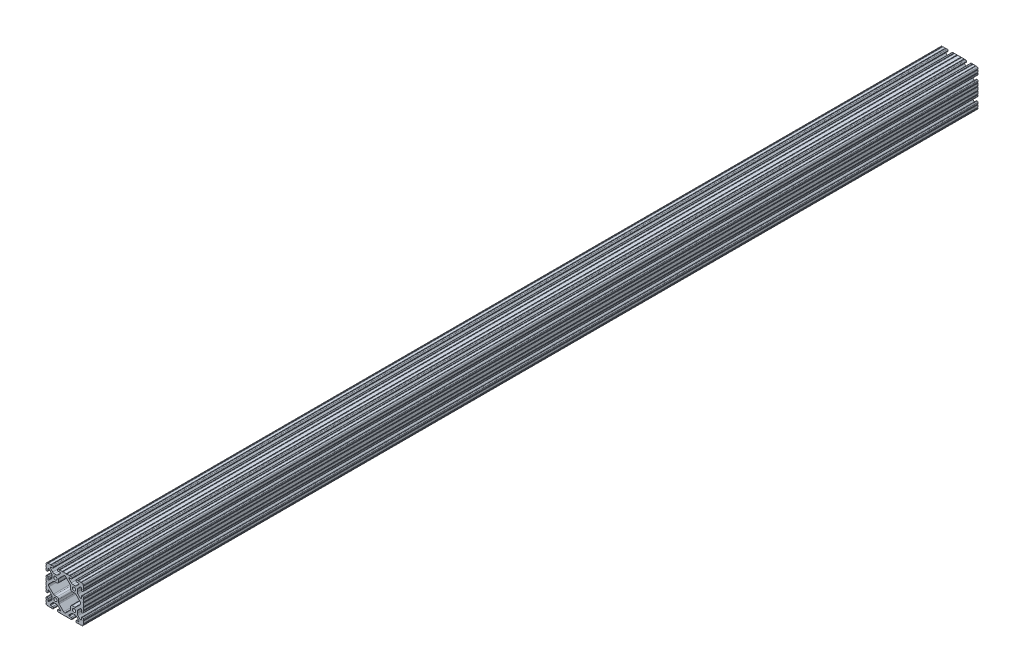
SolidWorks part; units mm, degrees
ref_plane "Front Plane" through (0, 0, 0) normal (0, 0, 1) x (1, 0, 0)
ref_plane "Top Plane" through (0, 0, 0) normal (0, 1, 0) x (1, 0, 0)
ref_plane "Right Plane" through (0, 0, 0) normal (1, 0, 0) x (0, 0, -1)
sketch "Sketch1" plane through (0, 0, 0) normal (0, 0, 1) x (1, 0, 0)
  line L0 (0, 38.1) -> (0, -38.1) construction
  line L1 (-38.1, -38.1) -> (38.1, -38.1) construction
  line L2 (-38.1, -38.1) -> (-38.1, 38.1) construction
  line L3 (-38.1, 38.1) -> (38.1, 38.1) construction
  line L4 (38.1, -38.1) -> (38.1, 38.1) construction
  line L5 (0, 38.1) -> (0, -38.1) construction
  line L6 (-38.1, 0) -> (38.1, 0) construction
  line L7 (-19.05, 19.05) -> (19.05, 19.05) construction
  line L8 (-19.05, 19.05) -> (-19.05, -19.05) construction
  line L9 (-19.05, -19.05) -> (19.05, -19.05) construction
  line L10 (19.05, 19.05) -> (19.05, -19.05) construction
  line L11 (-23.114, 38.1) -> (-23.114, -38.1) construction
  line L12 (-23.114, -38.1) -> (-14.986, 38.1) construction
  line L13 (-14.986, 38.1) -> (-14.986, -38.1) construction
  circle A0 centre (19.05, 19.05) radius 3.3274
  point P0 (0, 0)
  point P9 (0, 0)
  point P12 (-19.05, 0)
  line B0 (-11.3637, -22.8433) -> (-2.0515, -32.1555)
  line B1 (-12.2936, -15.4686) -> (-12.2936, -20.5983)
  line B2 (-20.769, -12.2936) -> (-15.4686, -12.2936)
  line B3 (-31.9021, -2.4756) -> (-23.0141, -11.3637)
  line B4 (-23.0141, 11.3637) -> (-31.9021, 2.4756)
  line B5 (-15.4686, 12.2936) -> (-20.769, 12.2936)
  line B6 (-12.2936, 20.5983) -> (-12.2936, 15.4686)
  line B7 (-2.0515, 32.1555) -> (-11.3637, 22.8433)
  line B8 (11.3637, 22.8433) -> (2.0515, 32.1555)
  line B9 (12.2936, 15.4686) -> (12.2936, 20.5983)
  line B10 (20.769, 12.2936) -> (15.4686, 12.2936)
  line B11 (31.9021, 2.4756) -> (23.0141, 11.3637)
  line B12 (23.0141, -11.3637) -> (31.9021, -2.4756)
  line B13 (15.4686, -12.2936) -> (20.769, -12.2936)
  line B14 (12.2936, -20.5983) -> (12.2936, -15.4686)
  line B15 (2.0515, -32.1555) -> (11.3637, -22.8433)
  line B16 (-4.7773, 38.1) -> (-9.6053, 38.1)
  line B17 (-11.1289, 38.1) -> (-13.4112, 38.1)
  line B18 (-14.986, 36.5252) -> (-14.986, 35.6108)
  line B19 (-13.4112, 34.036) -> (-9.652, 34.036)
  line B20 (-8.763, 33.147) -> (-8.763, 32.4935)
  line B21 (-9.0234, 31.8649) -> (-13.6907, 27.1976)
  line B22 (-17.0493, 25.8064) -> (-21.0507, 25.8064)
  line B23 (-24.4093, 27.1976) -> (-29.1002, 31.8885)
  line B24 (-29.337, 32.7207) -> (-29.337, 33.147)
  line B25 (-28.448, 34.036) -> (-24.6888, 34.036)
  line B26 (-23.114, 35.6108) -> (-23.114, 36.5252)
  line B27 (-24.6888, 38.1) -> (-27.0772, 38.1)
  line B28 (-28.6011, 38.1) -> (-33.4288, 38.1)
  line B29 (-38.1, 33.373) -> (-38.1, 28.5453)
  line B30 (-38.1, 27.0238) -> (-38.1, 24.6302)
  line B31 (-36.5252, 23.0554) -> (-35.6108, 23.0554)
  line B32 (-34.036, 24.6302) -> (-34.036, 28.448)
  line B33 (-33.147, 29.337) -> (-32.6643, 29.337)
  line B34 (-32.0357, 29.0766) -> (-27.1976, 24.2385)
  line B35 (-25.8064, 20.8799) -> (-25.8064, 17.2201)
  line B36 (-27.1976, 13.8615) -> (-31.9489, 9.1101)
  line B37 (-32.7869, 8.763) -> (-33.0603, 8.763)
  line B38 (-34.036, 9.7387) -> (-34.036, 13.4698)
  line B39 (-35.6108, 15.0446) -> (-36.5252, 15.0446)
  line B40 (-38.1, 13.4698) -> (-38.1, 11.075)
  line B41 (-38.1, 9.552) -> (-38.1, 4.7238)
  line B42 (-38.1, 3.2007) -> (-38.1, -3.2007)
  line B43 (-38.1, -4.7238) -> (-38.1, -9.552)
  line B44 (-38.1, -11.075) -> (-38.1, -13.4698)
  line B45 (-36.5252, -15.0446) -> (-35.6108, -15.0446)
  line B46 (-34.036, -13.4698) -> (-34.036, -9.7387)
  line B47 (-33.0603, -8.763) -> (-32.7869, -8.763)
  line B48 (-31.9489, -9.1101) -> (-27.1976, -13.8615)
  line B49 (-25.8064, -17.2201) -> (-25.8064, -20.8799)
  line B50 (-27.1976, -24.2385) -> (-32.0357, -29.0766)
  line B51 (-32.6643, -29.337) -> (-33.147, -29.337)
  line B52 (-34.036, -28.448) -> (-34.036, -24.6302)
  line B53 (-35.6108, -23.0554) -> (-36.5252, -23.0554)
  line B54 (-38.1, -24.6302) -> (-38.1, -27.0238)
  line B55 (-38.1, -28.5453) -> (-38.1, -33.373)
  line B56 (-33.4288, -38.1) -> (-28.6011, -38.1)
  line B57 (-27.0772, -38.1) -> (-24.6888, -38.1)
  line B58 (-23.114, -36.5252) -> (-23.114, -35.6108)
  line B59 (-24.6888, -34.036) -> (-28.448, -34.036)
  line B60 (-29.337, -33.147) -> (-29.337, -32.7207)
  line B61 (-29.1002, -31.8885) -> (-24.4093, -27.1976)
  line B62 (-21.0507, -25.8064) -> (-17.0493, -25.8064)
  line B63 (-13.6907, -27.1976) -> (-9.0234, -31.8649)
  line B64 (-8.763, -32.4935) -> (-8.763, -33.147)
  line B65 (-9.652, -34.036) -> (-13.4112, -34.036)
  line B66 (-14.986, -35.6108) -> (-14.986, -36.5252)
  line B67 (-13.4112, -38.1) -> (-11.1289, -38.1)
  line B68 (-9.6053, -38.1) -> (-4.7773, -38.1)
  line B69 (-3.2537, -38.1) -> (3.2537, -38.1)
  line B70 (4.7773, -38.1) -> (9.6053, -38.1)
  line B71 (11.1289, -38.1) -> (13.4112, -38.1)
  line B72 (14.986, -36.5252) -> (14.986, -35.6108)
  line B73 (13.4112, -34.036) -> (9.652, -34.036)
  line B74 (8.763, -33.147) -> (8.763, -32.4935)
  line B75 (9.0234, -31.8649) -> (13.6907, -27.1976)
  line B76 (17.0493, -25.8064) -> (21.0507, -25.8064)
  line B77 (24.4093, -27.1976) -> (29.1002, -31.8885)
  line B78 (29.337, -32.7207) -> (29.337, -33.147)
  line B79 (28.448, -34.036) -> (24.6888, -34.036)
  line B80 (23.114, -35.6108) -> (23.114, -36.5252)
  line B81 (24.6888, -38.1) -> (27.0772, -38.1)
  line B82 (28.6011, -38.1) -> (33.4288, -38.1)
  line B83 (38.1, -33.373) -> (38.1, -28.5453)
  line B84 (38.1, -27.0238) -> (38.1, -24.6302)
  line B85 (36.5252, -23.0554) -> (35.6108, -23.0554)
  line B86 (34.036, -24.6302) -> (34.036, -28.448)
  line B87 (33.147, -29.337) -> (32.6643, -29.337)
  line B88 (32.0357, -29.0766) -> (27.1976, -24.2385)
  line B89 (25.8064, -20.8799) -> (25.8064, -17.2201)
  line B90 (27.1976, -13.8615) -> (31.9489, -9.1101)
  line B91 (32.7869, -8.763) -> (33.0603, -8.763)
  line B92 (34.036, -9.7387) -> (34.036, -13.4698)
  line B93 (35.6108, -15.0446) -> (36.5252, -15.0446)
  line B94 (38.1, -13.4698) -> (38.1, -11.075)
  line B95 (38.1, -9.552) -> (38.1, -4.7238)
  line B96 (38.1, -3.2007) -> (38.1, 3.2007)
  line B97 (38.1, 4.7238) -> (38.1, 9.552)
  line B98 (38.1, 11.075) -> (38.1, 13.4698)
  line B99 (36.5252, 15.0446) -> (35.6108, 15.0446)
  line B100 (34.036, 13.4698) -> (34.036, 9.7387)
  line B101 (33.0603, 8.763) -> (32.7869, 8.763)
  line B102 (31.9489, 9.1101) -> (27.1976, 13.8615)
  line B103 (25.8064, 17.2201) -> (25.8064, 20.8799)
  line B104 (27.1976, 24.2385) -> (32.0357, 29.0766)
  line B105 (32.6643, 29.337) -> (33.147, 29.337)
  line B106 (34.036, 28.448) -> (34.036, 24.6302)
  line B107 (35.6108, 23.0554) -> (36.5252, 23.0554)
  line B108 (38.1, 24.6302) -> (38.1, 27.0238)
  line B109 (38.1, 28.5453) -> (38.1, 33.373)
  line B110 (33.4288, 38.1) -> (28.6011, 38.1)
  line B111 (27.0772, 38.1) -> (24.6888, 38.1)
  line B112 (23.114, 36.5252) -> (23.114, 35.6108)
  line B113 (24.6888, 34.036) -> (28.448, 34.036)
  line B114 (29.337, 33.147) -> (29.337, 32.7207)
  line B115 (29.1002, 31.8885) -> (24.4093, 27.1976)
  line B116 (21.0507, 25.8064) -> (17.0493, 25.8064)
  line B117 (13.6907, 27.1976) -> (9.0234, 31.8649)
  line B118 (8.763, 32.4935) -> (8.763, 33.147)
  line B119 (9.652, 34.036) -> (13.4112, 34.036)
  line B120 (14.986, 35.6108) -> (14.986, 36.5252)
  line B121 (13.4112, 38.1) -> (11.1289, 38.1)
  line B122 (9.6053, 38.1) -> (4.7773, 38.1)
  line B123 (3.2537, 38.1) -> (-3.2537, 38.1)
  circle B124 centre (-19.05, 19.05) radius 3.3274
  circle B125 centre (-19.05, -19.05) radius 3.3274
  circle B126 centre (19.05, -19.05) radius 3.3274
  circle B127 centre (19.05, 19.05) radius 3.3274
  arc B128 (0, -33.011) -> (2.0515, -32.1555) centre (-0.0139, -30.09) ccw
  arc B129 (-2.0515, -32.1555) -> (0, -33.011) centre (0.0139, -30.09) ccw
  arc B130 (-12.2936, -20.5983) -> (-11.3637, -22.8433) centre (-9.1186, -20.5983) ccw
  arc B131 (-12.2936, -15.4686) -> (-15.4686, -12.2936) centre (-15.4686, -15.4686) ccw
  arc B132 (-23.0141, -11.3637) -> (-20.769, -12.2936) centre (-20.769, -9.1186) ccw
  arc B133 (-32.7287, 0) -> (-31.9021, -2.4756) centre (-29.8367, -0.4102) ccw
  arc B134 (-31.9021, 2.4756) -> (-32.7287, 0) centre (-29.8367, 0.4102) ccw
  arc B135 (-20.769, 12.2936) -> (-23.0141, 11.3637) centre (-20.769, 9.1186) ccw
  arc B136 (-15.4686, 12.2936) -> (-12.2936, 15.4686) centre (-15.4686, 15.4686) ccw
  arc B137 (-11.3637, 22.8433) -> (-12.2936, 20.5983) centre (-9.1186, 20.5983) ccw
  arc B138 (0, 33.011) -> (-2.0515, 32.1555) centre (0.0139, 30.09) ccw
  arc B139 (2.0515, 32.1555) -> (0, 33.011) centre (-0.0139, 30.09) ccw
  arc B140 (12.2936, 20.5983) -> (11.3637, 22.8433) centre (9.1186, 20.5983) ccw
  arc B141 (12.2936, 15.4686) -> (15.4686, 12.2936) centre (15.4686, 15.4686) ccw
  arc B142 (23.0141, 11.3637) -> (20.769, 12.2936) centre (20.769, 9.1186) ccw
  arc B143 (32.7287, 0) -> (31.9021, 2.4756) centre (29.8367, 0.4102) ccw
  arc B144 (31.9021, -2.4756) -> (32.7287, 0) centre (29.8367, -0.4102) ccw
  arc B145 (20.769, -12.2936) -> (23.0141, -11.3637) centre (20.769, -9.1186) ccw
  arc B146 (15.4686, -12.2936) -> (12.2936, -15.4686) centre (15.4686, -15.4686) ccw
  arc B147 (11.3637, -22.8433) -> (12.2936, -20.5983) centre (9.1186, -20.5983) ccw
  arc B148 (-4.7773, 38.1) -> (-3.2537, 38.1) centre (-4.0155, 38.0824) ccw
  arc B149 (-11.1289, 38.1) -> (-9.6053, 38.1) centre (-10.3671, 38.0824) ccw
  arc B150 (-13.4112, 38.1) -> (-14.986, 36.5252) centre (-13.4112, 36.5252) ccw
  arc B151 (-14.986, 35.6108) -> (-13.4112, 34.036) centre (-13.4112, 35.6108) ccw
  arc B152 (-8.763, 33.147) -> (-9.652, 34.036) centre (-9.652, 33.147) ccw
  arc B153 (-9.0234, 31.8649) -> (-8.763, 32.4935) centre (-9.652, 32.4935) ccw
  arc B154 (-17.0493, 25.8064) -> (-13.6907, 27.1976) centre (-17.0493, 30.5562) ccw
  arc B155 (-24.4093, 27.1976) -> (-21.0507, 25.8064) centre (-21.0507, 30.5562) ccw
  arc B156 (-29.337, 32.7207) -> (-29.1002, 31.8885) centre (-28.4716, 32.5172) ccw
  arc B157 (-28.448, 34.036) -> (-29.337, 33.147) centre (-28.448, 33.147) ccw
  arc B158 (-24.6888, 34.036) -> (-23.114, 35.6108) centre (-24.6888, 35.6108) ccw
  arc B159 (-23.114, 36.5252) -> (-24.6888, 38.1) centre (-24.6888, 36.5252) ccw
  arc B160 (-28.6011, 38.1) -> (-27.0772, 38.1) centre (-27.8392, 38.0824) ccw
  arc B161 (-34.9527, 38.1) -> (-33.4288, 38.1) centre (-34.1907, 38.0824) ccw
  arc B162 (-34.9527, 38.1) -> (-37.0861, 37.1826) centre (-34.8521, 34.9266) ccw
  arc B163 (-37.0861, 37.1826) -> (-38.1, 34.8455) centre (-34.925, 34.8566) ccw
  arc B164 (-38.1, 33.373) -> (-38.1, 34.8455) centre (-37.9035, 34.1092) ccw
  arc B165 (-38.1, 27.0238) -> (-38.1, 28.5453) centre (-37.9035, 27.7845) ccw
  arc B166 (-38.1, 24.6302) -> (-36.5252, 23.0554) centre (-36.5252, 24.6302) ccw
  arc B167 (-35.6108, 23.0554) -> (-34.036, 24.6302) centre (-35.6108, 24.6302) ccw
  arc B168 (-33.147, 29.337) -> (-34.036, 28.448) centre (-33.147, 28.448) ccw
  arc B169 (-32.0357, 29.0766) -> (-32.6643, 29.337) centre (-32.6643, 28.448) ccw
  arc B170 (-25.8064, 20.8799) -> (-27.1976, 24.2385) centre (-30.5562, 20.8799) ccw
  arc B171 (-27.1976, 13.8615) -> (-25.8064, 17.2201) centre (-30.5562, 17.2201) ccw
  arc B172 (-32.7869, 8.763) -> (-31.9489, 9.1101) centre (-32.7869, 9.9481) ccw
  arc B173 (-34.036, 9.7387) -> (-33.0603, 8.763) centre (-33.0603, 9.7387) ccw
  arc B174 (-34.036, 13.4698) -> (-35.6108, 15.0446) centre (-35.6108, 13.4698) ccw
  arc B175 (-36.5252, 15.0446) -> (-38.1, 13.4698) centre (-36.5252, 13.4698) ccw
  arc B176 (-38.1, 9.552) -> (-38.1, 11.075) centre (-37.9035, 10.3135) ccw
  arc B177 (-38.1, 3.2007) -> (-38.1, 4.7238) centre (-37.9035, 3.9622) ccw
  arc B178 (-38.1, -4.7238) -> (-38.1, -3.2007) centre (-37.9035, -3.9622) ccw
  arc B179 (-38.1, -11.075) -> (-38.1, -9.552) centre (-37.9035, -10.3135) ccw
  arc B180 (-38.1, -13.4698) -> (-36.5252, -15.0446) centre (-36.5252, -13.4698) ccw
  arc B181 (-35.6108, -15.0446) -> (-34.036, -13.4698) centre (-35.6108, -13.4698) ccw
  arc B182 (-33.0603, -8.763) -> (-34.036, -9.7387) centre (-33.0603, -9.7387) ccw
  arc B183 (-31.9489, -9.1101) -> (-32.7869, -8.763) centre (-32.7869, -9.9481) ccw
  arc B184 (-25.8064, -17.2201) -> (-27.1976, -13.8615) centre (-30.5562, -17.2201) ccw
  arc B185 (-27.1976, -24.2385) -> (-25.8064, -20.8799) centre (-30.5562, -20.8799) ccw
  arc B186 (-32.6643, -29.337) -> (-32.0357, -29.0766) centre (-32.6643, -28.448) ccw
  arc B187 (-34.036, -28.448) -> (-33.147, -29.337) centre (-33.147, -28.448) ccw
  arc B188 (-34.036, -24.6302) -> (-35.6108, -23.0554) centre (-35.6108, -24.6302) ccw
  arc B189 (-36.5252, -23.0554) -> (-38.1, -24.6302) centre (-36.5252, -24.6302) ccw
  arc B190 (-38.1, -28.5453) -> (-38.1, -27.0238) centre (-37.9035, -27.7845) ccw
  arc B191 (-38.1, -34.8455) -> (-38.1, -33.373) centre (-37.9035, -34.1092) ccw
  arc B192 (-38.1, -34.8455) -> (-37.0861, -37.1826) centre (-34.925, -34.8566) ccw
  arc B193 (-37.0861, -37.1826) -> (-34.9527, -38.1) centre (-34.8521, -34.9266) ccw
  arc B194 (-33.4288, -38.1) -> (-34.9527, -38.1) centre (-34.1907, -38.0824) ccw
  arc B195 (-27.0772, -38.1) -> (-28.6011, -38.1) centre (-27.8392, -38.0824) ccw
  arc B196 (-24.6888, -38.1) -> (-23.114, -36.5252) centre (-24.6888, -36.5252) ccw
  arc B197 (-23.114, -35.6108) -> (-24.6888, -34.036) centre (-24.6888, -35.6108) ccw
  arc B198 (-29.337, -33.147) -> (-28.448, -34.036) centre (-28.448, -33.147) ccw
  arc B199 (-29.1002, -31.8885) -> (-29.337, -32.7207) centre (-28.4716, -32.5172) ccw
  arc B200 (-21.0507, -25.8064) -> (-24.4093, -27.1976) centre (-21.0507, -30.5562) ccw
  arc B201 (-13.6907, -27.1976) -> (-17.0493, -25.8064) centre (-17.0493, -30.5562) ccw
  arc B202 (-8.763, -32.4935) -> (-9.0234, -31.8649) centre (-9.652, -32.4935) ccw
  arc B203 (-9.652, -34.036) -> (-8.763, -33.147) centre (-9.652, -33.147) ccw
  arc B204 (-13.4112, -34.036) -> (-14.986, -35.6108) centre (-13.4112, -35.6108) ccw
  arc B205 (-14.986, -36.5252) -> (-13.4112, -38.1) centre (-13.4112, -36.5252) ccw
  arc B206 (-9.6053, -38.1) -> (-11.1289, -38.1) centre (-10.3671, -38.0824) ccw
  arc B207 (-3.2537, -38.1) -> (-4.7773, -38.1) centre (-4.0155, -38.0824) ccw
  arc B208 (4.7773, -38.1) -> (3.2537, -38.1) centre (4.0155, -38.0824) ccw
  arc B209 (11.1289, -38.1) -> (9.6053, -38.1) centre (10.3671, -38.0824) ccw
  arc B210 (13.4112, -38.1) -> (14.986, -36.5252) centre (13.4112, -36.5252) ccw
  arc B211 (14.986, -35.6108) -> (13.4112, -34.036) centre (13.4112, -35.6108) ccw
  arc B212 (8.763, -33.147) -> (9.652, -34.036) centre (9.652, -33.147) ccw
  arc B213 (9.0234, -31.8649) -> (8.763, -32.4935) centre (9.652, -32.4935) ccw
  arc B214 (17.0493, -25.8064) -> (13.6907, -27.1976) centre (17.0493, -30.5562) ccw
  arc B215 (24.4093, -27.1976) -> (21.0507, -25.8064) centre (21.0507, -30.5562) ccw
  arc B216 (29.337, -32.7207) -> (29.1002, -31.8885) centre (28.4716, -32.5172) ccw
  arc B217 (28.448, -34.036) -> (29.337, -33.147) centre (28.448, -33.147) ccw
  arc B218 (24.6888, -34.036) -> (23.114, -35.6108) centre (24.6888, -35.6108) ccw
  arc B219 (23.114, -36.5252) -> (24.6888, -38.1) centre (24.6888, -36.5252) ccw
  arc B220 (28.6011, -38.1) -> (27.0772, -38.1) centre (27.8392, -38.0824) ccw
  arc B221 (34.9527, -38.1) -> (33.4288, -38.1) centre (34.1907, -38.0824) ccw
  arc B222 (34.9527, -38.1) -> (37.0861, -37.1826) centre (34.8521, -34.9266) ccw
  arc B223 (37.0861, -37.1826) -> (38.1, -34.8455) centre (34.925, -34.8566) ccw
  arc B224 (38.1, -33.373) -> (38.1, -34.8455) centre (37.9035, -34.1092) ccw
  arc B225 (38.1, -27.0238) -> (38.1, -28.5453) centre (37.9035, -27.7845) ccw
  arc B226 (38.1, -24.6302) -> (36.5252, -23.0554) centre (36.5252, -24.6302) ccw
  arc B227 (35.6108, -23.0554) -> (34.036, -24.6302) centre (35.6108, -24.6302) ccw
  arc B228 (33.147, -29.337) -> (34.036, -28.448) centre (33.147, -28.448) ccw
  arc B229 (32.0357, -29.0766) -> (32.6643, -29.337) centre (32.6643, -28.448) ccw
  arc B230 (25.8064, -20.8799) -> (27.1976, -24.2385) centre (30.5562, -20.8799) ccw
  arc B231 (27.1976, -13.8615) -> (25.8064, -17.2201) centre (30.5562, -17.2201) ccw
  arc B232 (32.7869, -8.763) -> (31.9489, -9.1101) centre (32.7869, -9.9481) ccw
  arc B233 (34.036, -9.7387) -> (33.0603, -8.763) centre (33.0603, -9.7387) ccw
  arc B234 (34.036, -13.4698) -> (35.6108, -15.0446) centre (35.6108, -13.4698) ccw
  arc B235 (36.5252, -15.0446) -> (38.1, -13.4698) centre (36.5252, -13.4698) ccw
  arc B236 (38.1, -9.552) -> (38.1, -11.075) centre (37.9035, -10.3135) ccw
  arc B237 (38.1, -3.2007) -> (38.1, -4.7238) centre (37.9035, -3.9622) ccw
  arc B238 (38.1, 4.7238) -> (38.1, 3.2007) centre (37.9035, 3.9622) ccw
  arc B239 (38.1, 11.075) -> (38.1, 9.552) centre (37.9035, 10.3135) ccw
  arc B240 (38.1, 13.4698) -> (36.5252, 15.0446) centre (36.5252, 13.4698) ccw
  arc B241 (35.6108, 15.0446) -> (34.036, 13.4698) centre (35.6108, 13.4698) ccw
  arc B242 (33.0603, 8.763) -> (34.036, 9.7387) centre (33.0603, 9.7387) ccw
  arc B243 (31.9489, 9.1101) -> (32.7869, 8.763) centre (32.7869, 9.9481) ccw
  arc B244 (25.8064, 17.2201) -> (27.1976, 13.8615) centre (30.5562, 17.2201) ccw
  arc B245 (27.1976, 24.2385) -> (25.8064, 20.8799) centre (30.5562, 20.8799) ccw
  arc B246 (32.6643, 29.337) -> (32.0357, 29.0766) centre (32.6643, 28.448) ccw
  arc B247 (34.036, 28.448) -> (33.147, 29.337) centre (33.147, 28.448) ccw
  arc B248 (34.036, 24.6302) -> (35.6108, 23.0554) centre (35.6108, 24.6302) ccw
  arc B249 (36.5252, 23.0554) -> (38.1, 24.6302) centre (36.5252, 24.6302) ccw
  arc B250 (38.1, 28.5453) -> (38.1, 27.0238) centre (37.9035, 27.7845) ccw
  arc B251 (38.1, 34.8455) -> (38.1, 33.373) centre (37.9035, 34.1092) ccw
  arc B252 (38.1, 34.8455) -> (37.0861, 37.1826) centre (34.925, 34.8566) ccw
  arc B253 (37.0861, 37.1826) -> (34.9527, 38.1) centre (34.8521, 34.9266) ccw
  arc B254 (33.4288, 38.1) -> (34.9527, 38.1) centre (34.1907, 38.0824) ccw
  arc B255 (27.0772, 38.1) -> (28.6011, 38.1) centre (27.8392, 38.0824) ccw
  arc B256 (24.6888, 38.1) -> (23.114, 36.5252) centre (24.6888, 36.5252) ccw
  arc B257 (23.114, 35.6108) -> (24.6888, 34.036) centre (24.6888, 35.6108) ccw
  arc B258 (29.337, 33.147) -> (28.448, 34.036) centre (28.448, 33.147) ccw
  arc B259 (29.1002, 31.8885) -> (29.337, 32.7207) centre (28.4716, 32.5172) ccw
  arc B260 (21.0507, 25.8064) -> (24.4093, 27.1976) centre (21.0507, 30.5562) ccw
  arc B261 (13.6907, 27.1976) -> (17.0493, 25.8064) centre (17.0493, 30.5562) ccw
  arc B262 (8.763, 32.4935) -> (9.0234, 31.8649) centre (9.652, 32.4935) ccw
  arc B263 (9.652, 34.036) -> (8.763, 33.147) centre (9.652, 33.147) ccw
  arc B264 (13.4112, 34.036) -> (14.986, 35.6108) centre (13.4112, 35.6108) ccw
  arc B265 (14.986, 36.5252) -> (13.4112, 38.1) centre (13.4112, 36.5252) ccw
  arc B266 (9.6053, 38.1) -> (11.1289, 38.1) centre (10.3671, 38.0824) ccw
  arc B267 (3.2537, 38.1) -> (4.7773, 38.1) centre (4.0155, 38.0824) ccw
  dimension "Center Hole Diameter" = 6.6548
  dimension "Rail Width" = 76.2
  dimension "Rail Height" = 76.2
  dimension "T-Slot Width" = 8.128
sketch_block_instance "Block1-1"
sketch_block "Block1"
sketch "Sketch2" plane through (0, 0, 0) normal (1, 0, 0) x (0, 0, -1)
  line L0 (-914.4, 0) -> (914.4, 0) construction
  line L1 (-914.4, 38.1) -> (-914.4, -38.1) construction
  line L2 (-914.4, -38.1) -> (914.4, -38.1) construction
  line L3 (914.4, -38.1) -> (914.4, 38.1) construction
  line L4 (-812.8, 0) -> (-812.8, 38.1) construction
  line L5 (-812.8, 38.1) -> (812.8, 38.1) construction
  line L6 (812.8, 38.1) -> (812.8, 0) construction
  point P5 (812.8, 0)
  point P10 (-812.8, 0)
  dimension "D1" = 101.6
  dimension "Length" = 1828.8
  dimension "D2" = 101.6
sketch "Sketch3" plane through (0, 0, 0) normal (0, 0, 1) x (1, 0, 0)
  line L0 (-11.3637, -22.8433) -> (-2.0515, -32.1555) construction
  line L1 (-12.2936, -15.4686) -> (-12.2936, -20.5983) construction
  line L2 (-20.769, -12.2936) -> (-15.4686, -12.2936) construction
  line L3 (-31.9021, -2.4756) -> (-23.0141, -11.3637) construction
  line L4 (-23.0141, 11.3637) -> (-31.9021, 2.4756) construction
  line L5 (-15.4686, 12.2936) -> (-20.769, 12.2936) construction
  line L6 (-12.2936, 20.5983) -> (-12.2936, 15.4686) construction
  line L7 (-2.0515, 32.1555) -> (-11.3637, 22.8433) construction
  line L8 (11.3637, 22.8433) -> (2.0515, 32.1555) construction
  line L9 (12.2936, 15.4686) -> (12.2936, 20.5983) construction
  line L10 (20.769, 12.2936) -> (15.4686, 12.2936) construction
  line L11 (31.9021, 2.4756) -> (23.0141, 11.3637) construction
  line L12 (23.0141, -11.3637) -> (31.9021, -2.4756) construction
  line L13 (15.4686, -12.2936) -> (20.769, -12.2936) construction
  line L14 (12.2936, -20.5983) -> (12.2936, -15.4686) construction
  line L15 (2.0515, -32.1555) -> (11.3637, -22.8433) construction
  line L16 (34.036, 28.448) -> (34.036, 24.6302) construction
  line L17 (35.6108, 23.0554) -> (36.5252, 23.0554) construction
  line L18 (38.1, 24.6302) -> (38.1, 27.0238) construction
  line L19 (38.1, 28.5453) -> (38.1, 33.373) construction
  line L20 (33.4288, 38.1) -> (28.6011, 38.1) construction
  line L21 (27.0772, 38.1) -> (24.6888, 38.1) construction
  line L22 (23.114, 36.5252) -> (23.114, 35.6108) construction
  line L23 (24.6888, 34.036) -> (28.448, 34.036) construction
  line L24 (29.337, 33.147) -> (29.337, 32.7207) construction
  line L25 (29.1002, 31.8885) -> (24.4093, 27.1976) construction
  line L26 (21.0507, 25.8064) -> (17.0493, 25.8064) construction
  line L27 (13.6907, 27.1976) -> (9.0234, 31.8649) construction
  line L28 (8.763, 32.4935) -> (8.763, 33.147) construction
  line L29 (9.652, 34.036) -> (13.4112, 34.036) construction
  line L30 (14.986, 35.6108) -> (14.986, 36.5252) construction
  line L31 (13.4112, 38.1) -> (11.1289, 38.1) construction
  line L32 (9.6053, 38.1) -> (4.7773, 38.1) construction
  line L33 (3.2537, 38.1) -> (-3.2537, 38.1) construction
  line L34 (-4.7773, 38.1) -> (-9.6053, 38.1) construction
  line L35 (-11.1289, 38.1) -> (-13.4112, 38.1) construction
  line L36 (-14.986, 36.5252) -> (-14.986, 35.6108) construction
  line L37 (-13.4112, 34.036) -> (-9.652, 34.036) construction
  line L38 (-8.763, 33.147) -> (-8.763, 32.4935) construction
  line L39 (-9.0234, 31.8649) -> (-13.6907, 27.1976) construction
  line L40 (-17.0493, 25.8064) -> (-21.0507, 25.8064) construction
  line L41 (-24.4093, 27.1976) -> (-29.1002, 31.8885) construction
  line L42 (-29.337, 32.7207) -> (-29.337, 33.147) construction
  line L43 (-28.448, 34.036) -> (-24.6888, 34.036) construction
  line L44 (-23.114, 35.6108) -> (-23.114, 36.5252) construction
  line L45 (-24.6888, 38.1) -> (-27.0772, 38.1) construction
  line L46 (-28.6011, 38.1) -> (-33.4288, 38.1) construction
  line L47 (-38.1, 33.373) -> (-38.1, 28.5453) construction
  line L48 (-38.1, 27.0238) -> (-38.1, 24.6302) construction
  line L49 (-36.5252, 23.0554) -> (-35.6108, 23.0554) construction
  line L50 (-34.036, 24.6302) -> (-34.036, 28.448) construction
  line L51 (-33.147, 29.337) -> (-32.6643, 29.337) construction
  line L52 (-32.0357, 29.0766) -> (-27.1976, 24.2385) construction
  line L53 (-25.8064, 20.8799) -> (-25.8064, 17.2201) construction
  line L54 (-27.1976, 13.8615) -> (-31.9489, 9.1101) construction
  line L55 (-32.7869, 8.763) -> (-33.0603, 8.763) construction
  line L56 (-34.036, 9.7387) -> (-34.036, 13.4698) construction
  line L57 (-35.6108, 15.0446) -> (-36.5252, 15.0446) construction
  line L58 (-38.1, 13.4698) -> (-38.1, 11.075) construction
  line L59 (-38.1, 9.552) -> (-38.1, 4.7238) construction
  line L60 (-38.1, 3.2007) -> (-38.1, -3.2007) construction
  line L61 (-38.1, -4.7238) -> (-38.1, -9.552) construction
  line L62 (-38.1, -11.075) -> (-38.1, -13.4698) construction
  line L63 (-36.5252, -15.0446) -> (-35.6108, -15.0446) construction
  line L64 (-34.036, -13.4698) -> (-34.036, -9.7387) construction
  line L65 (-33.0603, -8.763) -> (-32.7869, -8.763) construction
  line L66 (-31.9489, -9.1101) -> (-27.1976, -13.8615) construction
  line L67 (-25.8064, -17.2201) -> (-25.8064, -20.8799) construction
  line L68 (-27.1976, -24.2385) -> (-32.0357, -29.0766) construction
  line L69 (-32.6643, -29.337) -> (-33.147, -29.337) construction
  line L70 (-34.036, -28.448) -> (-34.036, -24.6302) construction
  line L71 (-35.6108, -23.0554) -> (-36.5252, -23.0554) construction
  line L72 (-38.1, -24.6302) -> (-38.1, -27.0238) construction
  line L73 (-38.1, -28.5453) -> (-38.1, -33.373) construction
  line L74 (-33.4288, -38.1) -> (-28.6011, -38.1) construction
  line L75 (-27.0772, -38.1) -> (-24.6888, -38.1) construction
  line L76 (-23.114, -36.5252) -> (-23.114, -35.6108) construction
  line L77 (-24.6888, -34.036) -> (-28.448, -34.036) construction
  line L78 (-29.337, -33.147) -> (-29.337, -32.7207) construction
  line L79 (-29.1002, -31.8885) -> (-24.4093, -27.1976) construction
  line L80 (-21.0507, -25.8064) -> (-17.0493, -25.8064) construction
  line L81 (-13.6907, -27.1976) -> (-9.0234, -31.8649) construction
  line L82 (-8.763, -32.4935) -> (-8.763, -33.147) construction
  line L83 (-9.652, -34.036) -> (-13.4112, -34.036) construction
  line L84 (-14.986, -35.6108) -> (-14.986, -36.5252) construction
  line L85 (-13.4112, -38.1) -> (-11.1289, -38.1) construction
  line L86 (-9.6053, -38.1) -> (-4.7773, -38.1) construction
  line L87 (-3.2537, -38.1) -> (3.2537, -38.1) construction
  line L88 (4.7773, -38.1) -> (9.6053, -38.1) construction
  line L89 (11.1289, -38.1) -> (13.4112, -38.1) construction
  line L90 (14.986, -36.5252) -> (14.986, -35.6108) construction
  line L91 (13.4112, -34.036) -> (9.652, -34.036) construction
  line L92 (8.763, -33.147) -> (8.763, -32.4935) construction
  line L93 (9.0234, -31.8649) -> (13.6907, -27.1976) construction
  line L94 (17.0493, -25.8064) -> (21.0507, -25.8064) construction
  line L95 (24.4093, -27.1976) -> (29.1002, -31.8885) construction
  line L96 (29.337, -32.7207) -> (29.337, -33.147) construction
  line L97 (28.448, -34.036) -> (24.6888, -34.036) construction
  line L98 (23.114, -35.6108) -> (23.114, -36.5252) construction
  line L99 (24.6888, -38.1) -> (27.0772, -38.1) construction
  line L100 (28.6011, -38.1) -> (33.4288, -38.1) construction
  line L101 (38.1, -33.373) -> (38.1, -28.5453) construction
  line L102 (38.1, -27.0238) -> (38.1, -24.6302) construction
  line L103 (36.5252, -23.0554) -> (35.6108, -23.0554) construction
  line L104 (34.036, -24.6302) -> (34.036, -28.448) construction
  line L105 (33.147, -29.337) -> (32.6643, -29.337) construction
  line L106 (32.0357, -29.0766) -> (27.1976, -24.2385) construction
  line L107 (25.8064, -20.8799) -> (25.8064, -17.2201) construction
  line L108 (27.1976, -13.8615) -> (31.9489, -9.1101) construction
  line L109 (32.7869, -8.763) -> (33.0603, -8.763) construction
  line L110 (34.036, -9.7387) -> (34.036, -13.4698) construction
  line L111 (35.6108, -15.0446) -> (36.5252, -15.0446) construction
  line L112 (38.1, -13.4698) -> (38.1, -11.075) construction
  line L113 (38.1, -9.552) -> (38.1, -4.7238) construction
  line L114 (38.1, -3.2007) -> (38.1, 3.2007) construction
  line L115 (38.1, 4.7238) -> (38.1, 9.552) construction
  line L116 (38.1, 11.075) -> (38.1, 13.4698) construction
  line L117 (36.5252, 15.0446) -> (35.6108, 15.0446) construction
  line L118 (34.036, 13.4698) -> (34.036, 9.7387) construction
  line L119 (33.0603, 8.763) -> (32.7869, 8.763) construction
  line L120 (31.9489, 9.1101) -> (27.1976, 13.8615) construction
  line L121 (25.8064, 17.2201) -> (25.8064, 20.8799) construction
  line L122 (27.1976, 24.2385) -> (32.0357, 29.0766) construction
  line L123 (32.6643, 29.337) -> (33.147, 29.337) construction
  line L124 (-11.3637, -22.8433) -> (-2.0515, -32.1555)
  line L125 (-12.2936, -15.4686) -> (-12.2936, -20.5983)
  line L126 (-20.769, -12.2936) -> (-15.4686, -12.2936)
  line L127 (-31.9021, -2.4756) -> (-23.0141, -11.3637)
  line L128 (-23.0141, 11.3637) -> (-31.9021, 2.4756)
  line L129 (-15.4686, 12.2936) -> (-20.769, 12.2936)
  line L130 (-12.2936, 20.5983) -> (-12.2936, 15.4686)
  line L131 (-2.0515, 32.1555) -> (-11.3637, 22.8433)
  line L132 (11.3637, 22.8433) -> (2.0515, 32.1555)
  line L133 (12.2936, 15.4686) -> (12.2936, 20.5983)
  line L134 (20.769, 12.2936) -> (15.4686, 12.2936)
  line L135 (31.9021, 2.4756) -> (23.0141, 11.3637)
  line L136 (23.0141, -11.3637) -> (31.9021, -2.4756)
  line L137 (15.4686, -12.2936) -> (20.769, -12.2936)
  line L138 (12.2936, -20.5983) -> (12.2936, -15.4686)
  line L139 (2.0515, -32.1555) -> (11.3637, -22.8433)
  line L140 (34.036, 28.448) -> (34.036, 24.6302)
  line L141 (35.6108, 23.0554) -> (36.5252, 23.0554)
  line L142 (38.1, 24.6302) -> (38.1, 27.0238)
  line L143 (38.1, 28.5453) -> (38.1, 33.373)
  line L144 (33.4288, 38.1) -> (28.6011, 38.1)
  line L145 (27.0772, 38.1) -> (24.6888, 38.1)
  line L146 (23.114, 36.5252) -> (23.114, 35.6108)
  line L147 (24.6888, 34.036) -> (28.448, 34.036)
  line L148 (29.337, 33.147) -> (29.337, 32.7207)
  line L149 (29.1002, 31.8885) -> (24.4093, 27.1976)
  line L150 (21.0507, 25.8064) -> (17.0493, 25.8064)
  line L151 (13.6907, 27.1976) -> (9.0234, 31.8649)
  line L152 (8.763, 32.4935) -> (8.763, 33.147)
  line L153 (9.652, 34.036) -> (13.4112, 34.036)
  line L154 (14.986, 35.6108) -> (14.986, 36.5252)
  line L155 (13.4112, 38.1) -> (11.1289, 38.1)
  line L156 (9.6053, 38.1) -> (4.7773, 38.1)
  line L157 (3.2537, 38.1) -> (-3.2537, 38.1)
  line L158 (-4.7773, 38.1) -> (-9.6053, 38.1)
  line L159 (-11.1289, 38.1) -> (-13.4112, 38.1)
  line L160 (-14.986, 36.5252) -> (-14.986, 35.6108)
  line L161 (-13.4112, 34.036) -> (-9.652, 34.036)
  line L162 (-8.763, 33.147) -> (-8.763, 32.4935)
  line L163 (-9.0234, 31.8649) -> (-13.6907, 27.1976)
  line L164 (-17.0493, 25.8064) -> (-21.0507, 25.8064)
  line L165 (-24.4093, 27.1976) -> (-29.1002, 31.8885)
  line L166 (-29.337, 32.7207) -> (-29.337, 33.147)
  line L167 (-28.448, 34.036) -> (-24.6888, 34.036)
  line L168 (-23.114, 35.6108) -> (-23.114, 36.5252)
  line L169 (-24.6888, 38.1) -> (-27.0772, 38.1)
  line L170 (-28.6011, 38.1) -> (-33.4288, 38.1)
  line L171 (-38.1, 33.373) -> (-38.1, 28.5453)
  line L172 (-38.1, 27.0238) -> (-38.1, 24.6302)
  line L173 (-36.5252, 23.0554) -> (-35.6108, 23.0554)
  line L174 (-34.036, 24.6302) -> (-34.036, 28.448)
  line L175 (-33.147, 29.337) -> (-32.6643, 29.337)
  line L176 (-32.0357, 29.0766) -> (-27.1976, 24.2385)
  line L177 (-25.8064, 20.8799) -> (-25.8064, 17.2201)
  line L178 (-27.1976, 13.8615) -> (-31.9489, 9.1101)
  line L179 (-32.7869, 8.763) -> (-33.0603, 8.763)
  line L180 (-34.036, 9.7387) -> (-34.036, 13.4698)
  line L181 (-35.6108, 15.0446) -> (-36.5252, 15.0446)
  line L182 (-38.1, 13.4698) -> (-38.1, 11.075)
  line L183 (-38.1, 9.552) -> (-38.1, 4.7238)
  line L184 (-38.1, 3.2007) -> (-38.1, -3.2007)
  line L185 (-38.1, -4.7238) -> (-38.1, -9.552)
  line L186 (-38.1, -11.075) -> (-38.1, -13.4698)
  line L187 (-36.5252, -15.0446) -> (-35.6108, -15.0446)
  line L188 (-34.036, -13.4698) -> (-34.036, -9.7387)
  line L189 (-33.0603, -8.763) -> (-32.7869, -8.763)
  line L190 (-31.9489, -9.1101) -> (-27.1976, -13.8615)
  line L191 (-25.8064, -17.2201) -> (-25.8064, -20.8799)
  line L192 (-27.1976, -24.2385) -> (-32.0357, -29.0766)
  line L193 (-32.6643, -29.337) -> (-33.147, -29.337)
  line L194 (-34.036, -28.448) -> (-34.036, -24.6302)
  line L195 (-35.6108, -23.0554) -> (-36.5252, -23.0554)
  line L196 (-38.1, -24.6302) -> (-38.1, -27.0238)
  line L197 (-38.1, -28.5453) -> (-38.1, -33.373)
  line L198 (-33.4288, -38.1) -> (-28.6011, -38.1)
  line L199 (-27.0772, -38.1) -> (-24.6888, -38.1)
  line L200 (-23.114, -36.5252) -> (-23.114, -35.6108)
  line L201 (-24.6888, -34.036) -> (-28.448, -34.036)
  line L202 (-29.337, -33.147) -> (-29.337, -32.7207)
  line L203 (-29.1002, -31.8885) -> (-24.4093, -27.1976)
  line L204 (-21.0507, -25.8064) -> (-17.0493, -25.8064)
  line L205 (-13.6907, -27.1976) -> (-9.0234, -31.8649)
  line L206 (-8.763, -32.4935) -> (-8.763, -33.147)
  line L207 (-9.652, -34.036) -> (-13.4112, -34.036)
  line L208 (-14.986, -35.6108) -> (-14.986, -36.5252)
  line L209 (-13.4112, -38.1) -> (-11.1289, -38.1)
  line L210 (-9.6053, -38.1) -> (-4.7773, -38.1)
  line L211 (-3.2537, -38.1) -> (3.2537, -38.1)
  line L212 (4.7773, -38.1) -> (9.6053, -38.1)
  line L213 (11.1289, -38.1) -> (13.4112, -38.1)
  line L214 (14.986, -36.5252) -> (14.986, -35.6108)
  line L215 (13.4112, -34.036) -> (9.652, -34.036)
  line L216 (8.763, -33.147) -> (8.763, -32.4935)
  line L217 (9.0234, -31.8649) -> (13.6907, -27.1976)
  line L218 (17.0493, -25.8064) -> (21.0507, -25.8064)
  line L219 (24.4093, -27.1976) -> (29.1002, -31.8885)
  line L220 (29.337, -32.7207) -> (29.337, -33.147)
  line L221 (28.448, -34.036) -> (24.6888, -34.036)
  line L222 (23.114, -35.6108) -> (23.114, -36.5252)
  line L223 (24.6888, -38.1) -> (27.0772, -38.1)
  line L224 (28.6011, -38.1) -> (33.4288, -38.1)
  line L225 (38.1, -33.373) -> (38.1, -28.5453)
  line L226 (38.1, -27.0238) -> (38.1, -24.6302)
  line L227 (36.5252, -23.0554) -> (35.6108, -23.0554)
  line L228 (34.036, -24.6302) -> (34.036, -28.448)
  line L229 (33.147, -29.337) -> (32.6643, -29.337)
  line L230 (32.0357, -29.0766) -> (27.1976, -24.2385)
  line L231 (25.8064, -20.8799) -> (25.8064, -17.2201)
  line L232 (27.1976, -13.8615) -> (31.9489, -9.1101)
  line L233 (32.7869, -8.763) -> (33.0603, -8.763)
  line L234 (34.036, -9.7387) -> (34.036, -13.4698)
  line L235 (35.6108, -15.0446) -> (36.5252, -15.0446)
  line L236 (38.1, -13.4698) -> (38.1, -11.075)
  line L237 (38.1, -9.552) -> (38.1, -4.7238)
  line L238 (38.1, -3.2007) -> (38.1, 3.2007)
  line L239 (38.1, 4.7238) -> (38.1, 9.552)
  line L240 (38.1, 11.075) -> (38.1, 13.4698)
  line L241 (36.5252, 15.0446) -> (35.6108, 15.0446)
  line L242 (34.036, 13.4698) -> (34.036, 9.7387)
  line L243 (33.0603, 8.763) -> (32.7869, 8.763)
  line L244 (31.9489, 9.1101) -> (27.1976, 13.8615)
  line L245 (25.8064, 17.2201) -> (25.8064, 20.8799)
  line L246 (27.1976, 24.2385) -> (32.0357, 29.0766)
  line L247 (32.6643, 29.337) -> (33.147, 29.337)
  arc A0 (-2.0515, -32.1555) -> (0, -33.011) centre (0.0139, -30.09) ccw construction
  circle A1 centre (19.05, 19.05) radius 3.3274
  circle A2 centre (19.05, 19.05) radius 3.3274
  arc A3 (-12.2936, -20.5983) -> (-11.3637, -22.8433) centre (-9.1186, -20.5983) ccw construction
  arc A4 (-12.2936, -15.4686) -> (-15.4686, -12.2936) centre (-15.4686, -15.4686) ccw construction
  arc A5 (-23.0141, -11.3637) -> (-20.769, -12.2936) centre (-20.769, -9.1186) ccw construction
  arc A6 (-32.7287, 0) -> (-31.9021, -2.4756) centre (-29.8367, -0.4102) ccw construction
  arc A7 (-31.9021, 2.4756) -> (-32.7287, 0) centre (-29.8367, 0.4102) ccw construction
  arc A8 (-20.769, 12.2936) -> (-23.0141, 11.3637) centre (-20.769, 9.1186) ccw construction
  arc A9 (-15.4686, 12.2936) -> (-12.2936, 15.4686) centre (-15.4686, 15.4686) ccw construction
  arc A10 (-11.3637, 22.8433) -> (-12.2936, 20.5983) centre (-9.1186, 20.5983) ccw construction
  arc A11 (0, 33.011) -> (-2.0515, 32.1555) centre (0.0139, 30.09) ccw construction
  arc A12 (2.0515, 32.1555) -> (0, 33.011) centre (-0.0139, 30.09) ccw construction
  arc A13 (12.2936, 20.5983) -> (11.3637, 22.8433) centre (9.1186, 20.5983) ccw construction
  arc A14 (12.2936, 15.4686) -> (15.4686, 12.2936) centre (15.4686, 15.4686) ccw construction
  arc A15 (23.0141, 11.3637) -> (20.769, 12.2936) centre (20.769, 9.1186) ccw construction
  arc A16 (32.7287, 0) -> (31.9021, 2.4756) centre (29.8367, 0.4102) ccw construction
  arc A17 (31.9021, -2.4756) -> (32.7287, 0) centre (29.8367, -0.4102) ccw construction
  arc A18 (20.769, -12.2936) -> (23.0141, -11.3637) centre (20.769, -9.1186) ccw construction
  arc A19 (15.4686, -12.2936) -> (12.2936, -15.4686) centre (15.4686, -15.4686) ccw construction
  arc A20 (11.3637, -22.8433) -> (12.2936, -20.5983) centre (9.1186, -20.5983) ccw construction
  arc A21 (0, -33.011) -> (2.0515, -32.1555) centre (-0.0139, -30.09) ccw construction
  circle A22 centre (-19.05, 19.05) radius 3.3274 construction
  circle A23 centre (19.05, -19.05) radius 3.3274 construction
  circle A24 centre (-19.05, -19.05) radius 3.3274 construction
  circle A25 centre (19.05, 19.05) radius 3.3274 construction
  arc A26 (34.036, 24.6302) -> (35.6108, 23.0554) centre (35.6108, 24.6302) ccw construction
  arc A27 (36.5252, 23.0554) -> (38.1, 24.6302) centre (36.5252, 24.6302) ccw construction
  arc A28 (38.1, 28.5453) -> (38.1, 27.0238) centre (37.9035, 27.7845) ccw construction
  arc A29 (38.1, 34.8455) -> (38.1, 33.373) centre (37.9035, 34.1092) ccw construction
  arc A30 (38.1, 34.8455) -> (37.0861, 37.1826) centre (34.925, 34.8566) ccw construction
  arc A31 (37.0861, 37.1826) -> (34.9527, 38.1) centre (34.8521, 34.9266) ccw construction
  arc A32 (33.4288, 38.1) -> (34.9527, 38.1) centre (34.1907, 38.0824) ccw construction
  arc A33 (27.0772, 38.1) -> (28.6011, 38.1) centre (27.8392, 38.0824) ccw construction
  arc A34 (24.6888, 38.1) -> (23.114, 36.5252) centre (24.6888, 36.5252) ccw construction
  arc A35 (23.114, 35.6108) -> (24.6888, 34.036) centre (24.6888, 35.6108) ccw construction
  arc A36 (29.337, 33.147) -> (28.448, 34.036) centre (28.448, 33.147) ccw construction
  arc A37 (29.1002, 31.8885) -> (29.337, 32.7207) centre (28.4716, 32.5172) ccw construction
  arc A38 (21.0507, 25.8064) -> (24.4093, 27.1976) centre (21.0507, 30.5562) ccw construction
  arc A39 (13.6907, 27.1976) -> (17.0493, 25.8064) centre (17.0493, 30.5562) ccw construction
  arc A40 (8.763, 32.4935) -> (9.0234, 31.8649) centre (9.652, 32.4935) ccw construction
  arc A41 (9.652, 34.036) -> (8.763, 33.147) centre (9.652, 33.147) ccw construction
  arc A42 (13.4112, 34.036) -> (14.986, 35.6108) centre (13.4112, 35.6108) ccw construction
  arc A43 (14.986, 36.5252) -> (13.4112, 38.1) centre (13.4112, 36.5252) ccw construction
  arc A44 (9.6053, 38.1) -> (11.1289, 38.1) centre (10.3671, 38.0824) ccw construction
  arc A45 (3.2537, 38.1) -> (4.7773, 38.1) centre (4.0155, 38.0824) ccw construction
  arc A46 (-4.7773, 38.1) -> (-3.2537, 38.1) centre (-4.0155, 38.0824) ccw construction
  arc A47 (-11.1289, 38.1) -> (-9.6053, 38.1) centre (-10.3671, 38.0824) ccw construction
  arc A48 (-13.4112, 38.1) -> (-14.986, 36.5252) centre (-13.4112, 36.5252) ccw construction
  arc A49 (-14.986, 35.6108) -> (-13.4112, 34.036) centre (-13.4112, 35.6108) ccw construction
  arc A50 (-8.763, 33.147) -> (-9.652, 34.036) centre (-9.652, 33.147) ccw construction
  arc A51 (-9.0234, 31.8649) -> (-8.763, 32.4935) centre (-9.652, 32.4935) ccw construction
  arc A52 (-17.0493, 25.8064) -> (-13.6907, 27.1976) centre (-17.0493, 30.5562) ccw construction
  arc A53 (-24.4093, 27.1976) -> (-21.0507, 25.8064) centre (-21.0507, 30.5562) ccw construction
  arc A54 (-29.337, 32.7207) -> (-29.1002, 31.8885) centre (-28.4716, 32.5172) ccw construction
  arc A55 (-28.448, 34.036) -> (-29.337, 33.147) centre (-28.448, 33.147) ccw construction
  arc A56 (-24.6888, 34.036) -> (-23.114, 35.6108) centre (-24.6888, 35.6108) ccw construction
  arc A57 (-23.114, 36.5252) -> (-24.6888, 38.1) centre (-24.6888, 36.5252) ccw construction
  arc A58 (-28.6011, 38.1) -> (-27.0772, 38.1) centre (-27.8392, 38.0824) ccw construction
  arc A59 (-34.9527, 38.1) -> (-33.4288, 38.1) centre (-34.1907, 38.0824) ccw construction
  arc A60 (-34.9527, 38.1) -> (-37.0861, 37.1826) centre (-34.8521, 34.9266) ccw construction
  arc A61 (-37.0861, 37.1826) -> (-38.1, 34.8455) centre (-34.925, 34.8566) ccw construction
  arc A62 (-38.1, 33.373) -> (-38.1, 34.8455) centre (-37.9035, 34.1092) ccw construction
  arc A63 (-38.1, 27.0238) -> (-38.1, 28.5453) centre (-37.9035, 27.7845) ccw construction
  arc A64 (-38.1, 24.6302) -> (-36.5252, 23.0554) centre (-36.5252, 24.6302) ccw construction
  arc A65 (-35.6108, 23.0554) -> (-34.036, 24.6302) centre (-35.6108, 24.6302) ccw construction
  arc A66 (-33.147, 29.337) -> (-34.036, 28.448) centre (-33.147, 28.448) ccw construction
  arc A67 (-32.0357, 29.0766) -> (-32.6643, 29.337) centre (-32.6643, 28.448) ccw construction
  arc A68 (-25.8064, 20.8799) -> (-27.1976, 24.2385) centre (-30.5562, 20.8799) ccw construction
  arc A69 (-27.1976, 13.8615) -> (-25.8064, 17.2201) centre (-30.5562, 17.2201) ccw construction
  arc A70 (-32.7869, 8.763) -> (-31.9489, 9.1101) centre (-32.7869, 9.9481) ccw construction
  arc A71 (-34.036, 9.7387) -> (-33.0603, 8.763) centre (-33.0603, 9.7387) ccw construction
  arc A72 (-34.036, 13.4698) -> (-35.6108, 15.0446) centre (-35.6108, 13.4698) ccw construction
  arc A73 (-36.5252, 15.0446) -> (-38.1, 13.4698) centre (-36.5252, 13.4698) ccw construction
  arc A74 (-38.1, 9.552) -> (-38.1, 11.075) centre (-37.9035, 10.3135) ccw construction
  arc A75 (-38.1, 3.2007) -> (-38.1, 4.7238) centre (-37.9035, 3.9622) ccw construction
  arc A76 (-38.1, -4.7238) -> (-38.1, -3.2007) centre (-37.9035, -3.9622) ccw construction
  arc A77 (-38.1, -11.075) -> (-38.1, -9.552) centre (-37.9035, -10.3135) ccw construction
  arc A78 (-38.1, -13.4698) -> (-36.5252, -15.0446) centre (-36.5252, -13.4698) ccw construction
  arc A79 (-35.6108, -15.0446) -> (-34.036, -13.4698) centre (-35.6108, -13.4698) ccw construction
  arc A80 (-33.0603, -8.763) -> (-34.036, -9.7387) centre (-33.0603, -9.7387) ccw construction
  arc A81 (-31.9489, -9.1101) -> (-32.7869, -8.763) centre (-32.7869, -9.9481) ccw construction
  arc A82 (-25.8064, -17.2201) -> (-27.1976, -13.8615) centre (-30.5562, -17.2201) ccw construction
  arc A83 (-27.1976, -24.2385) -> (-25.8064, -20.8799) centre (-30.5562, -20.8799) ccw construction
  arc A84 (-32.6643, -29.337) -> (-32.0357, -29.0766) centre (-32.6643, -28.448) ccw construction
  arc A85 (-34.036, -28.448) -> (-33.147, -29.337) centre (-33.147, -28.448) ccw construction
  arc A86 (-34.036, -24.6302) -> (-35.6108, -23.0554) centre (-35.6108, -24.6302) ccw construction
  arc A87 (-36.5252, -23.0554) -> (-38.1, -24.6302) centre (-36.5252, -24.6302) ccw construction
  arc A88 (-38.1, -28.5453) -> (-38.1, -27.0238) centre (-37.9035, -27.7845) ccw construction
  arc A89 (-38.1, -34.8455) -> (-38.1, -33.373) centre (-37.9035, -34.1092) ccw construction
  arc A90 (-38.1, -34.8455) -> (-37.0861, -37.1826) centre (-34.925, -34.8566) ccw construction
  arc A91 (-37.0861, -37.1826) -> (-34.9527, -38.1) centre (-34.8521, -34.9266) ccw construction
  arc A92 (-33.4288, -38.1) -> (-34.9527, -38.1) centre (-34.1907, -38.0824) ccw construction
  arc A93 (-27.0772, -38.1) -> (-28.6011, -38.1) centre (-27.8392, -38.0824) ccw construction
  arc A94 (-24.6888, -38.1) -> (-23.114, -36.5252) centre (-24.6888, -36.5252) ccw construction
  arc A95 (-23.114, -35.6108) -> (-24.6888, -34.036) centre (-24.6888, -35.6108) ccw construction
  arc A96 (-29.337, -33.147) -> (-28.448, -34.036) centre (-28.448, -33.147) ccw construction
  arc A97 (-29.1002, -31.8885) -> (-29.337, -32.7207) centre (-28.4716, -32.5172) ccw construction
  arc A98 (-21.0507, -25.8064) -> (-24.4093, -27.1976) centre (-21.0507, -30.5562) ccw construction
  arc A99 (-13.6907, -27.1976) -> (-17.0493, -25.8064) centre (-17.0493, -30.5562) ccw construction
  arc A100 (-8.763, -32.4935) -> (-9.0234, -31.8649) centre (-9.652, -32.4935) ccw construction
  arc A101 (-9.652, -34.036) -> (-8.763, -33.147) centre (-9.652, -33.147) ccw construction
  arc A102 (-13.4112, -34.036) -> (-14.986, -35.6108) centre (-13.4112, -35.6108) ccw construction
  arc A103 (-14.986, -36.5252) -> (-13.4112, -38.1) centre (-13.4112, -36.5252) ccw construction
  arc A104 (-9.6053, -38.1) -> (-11.1289, -38.1) centre (-10.3671, -38.0824) ccw construction
  arc A105 (-3.2537, -38.1) -> (-4.7773, -38.1) centre (-4.0155, -38.0824) ccw construction
  arc A106 (4.7773, -38.1) -> (3.2537, -38.1) centre (4.0155, -38.0824) ccw construction
  arc A107 (11.1289, -38.1) -> (9.6053, -38.1) centre (10.3671, -38.0824) ccw construction
  arc A108 (13.4112, -38.1) -> (14.986, -36.5252) centre (13.4112, -36.5252) ccw construction
  arc A109 (14.986, -35.6108) -> (13.4112, -34.036) centre (13.4112, -35.6108) ccw construction
  arc A110 (8.763, -33.147) -> (9.652, -34.036) centre (9.652, -33.147) ccw construction
  arc A111 (9.0234, -31.8649) -> (8.763, -32.4935) centre (9.652, -32.4935) ccw construction
  arc A112 (17.0493, -25.8064) -> (13.6907, -27.1976) centre (17.0493, -30.5562) ccw construction
  arc A113 (24.4093, -27.1976) -> (21.0507, -25.8064) centre (21.0507, -30.5562) ccw construction
  arc A114 (29.337, -32.7207) -> (29.1002, -31.8885) centre (28.4716, -32.5172) ccw construction
  arc A115 (28.448, -34.036) -> (29.337, -33.147) centre (28.448, -33.147) ccw construction
  arc A116 (24.6888, -34.036) -> (23.114, -35.6108) centre (24.6888, -35.6108) ccw construction
  arc A117 (23.114, -36.5252) -> (24.6888, -38.1) centre (24.6888, -36.5252) ccw construction
  arc A118 (28.6011, -38.1) -> (27.0772, -38.1) centre (27.8392, -38.0824) ccw construction
  arc A119 (34.9527, -38.1) -> (33.4288, -38.1) centre (34.1907, -38.0824) ccw construction
  arc A120 (34.9527, -38.1) -> (37.0861, -37.1826) centre (34.8521, -34.9266) ccw construction
  arc A121 (37.0861, -37.1826) -> (38.1, -34.8455) centre (34.925, -34.8566) ccw construction
  arc A122 (38.1, -33.373) -> (38.1, -34.8455) centre (37.9035, -34.1092) ccw construction
  arc A123 (38.1, -27.0238) -> (38.1, -28.5453) centre (37.9035, -27.7845) ccw construction
  arc A124 (38.1, -24.6302) -> (36.5252, -23.0554) centre (36.5252, -24.6302) ccw construction
  arc A125 (35.6108, -23.0554) -> (34.036, -24.6302) centre (35.6108, -24.6302) ccw construction
  arc A126 (33.147, -29.337) -> (34.036, -28.448) centre (33.147, -28.448) ccw construction
  arc A127 (32.0357, -29.0766) -> (32.6643, -29.337) centre (32.6643, -28.448) ccw construction
  arc A128 (25.8064, -20.8799) -> (27.1976, -24.2385) centre (30.5562, -20.8799) ccw construction
  arc A129 (27.1976, -13.8615) -> (25.8064, -17.2201) centre (30.5562, -17.2201) ccw construction
  arc A130 (32.7869, -8.763) -> (31.9489, -9.1101) centre (32.7869, -9.9481) ccw construction
  arc A131 (34.036, -9.7387) -> (33.0603, -8.763) centre (33.0603, -9.7387) ccw construction
  arc A132 (34.036, -13.4698) -> (35.6108, -15.0446) centre (35.6108, -13.4698) ccw construction
  arc A133 (36.5252, -15.0446) -> (38.1, -13.4698) centre (36.5252, -13.4698) ccw construction
  arc A134 (38.1, -9.552) -> (38.1, -11.075) centre (37.9035, -10.3135) ccw construction
  arc A135 (38.1, -3.2007) -> (38.1, -4.7238) centre (37.9035, -3.9622) ccw construction
  arc A136 (38.1, 4.7238) -> (38.1, 3.2007) centre (37.9035, 3.9622) ccw construction
  arc A137 (38.1, 11.075) -> (38.1, 9.552) centre (37.9035, 10.3135) ccw construction
  arc A138 (38.1, 13.4698) -> (36.5252, 15.0446) centre (36.5252, 13.4698) ccw construction
  arc A139 (35.6108, 15.0446) -> (34.036, 13.4698) centre (35.6108, 13.4698) ccw construction
  arc A140 (33.0603, 8.763) -> (34.036, 9.7387) centre (33.0603, 9.7387) ccw construction
  arc A141 (31.9489, 9.1101) -> (32.7869, 8.763) centre (32.7869, 9.9481) ccw construction
  arc A142 (25.8064, 17.2201) -> (27.1976, 13.8615) centre (30.5562, 17.2201) ccw construction
  arc A143 (27.1976, 24.2385) -> (25.8064, 20.8799) centre (30.5562, 20.8799) ccw construction
  arc A144 (32.6643, 29.337) -> (32.0357, 29.0766) centre (32.6643, 28.448) ccw construction
  arc A145 (34.036, 28.448) -> (33.147, 29.337) centre (33.147, 28.448) ccw construction
  arc A146 (-2.0515, -32.1555) -> (0, -33.011) centre (0.0139, -30.09) ccw
  arc A147 (-12.2936, -20.5983) -> (-11.3637, -22.8433) centre (-9.1186, -20.5983) ccw
  arc A148 (-12.2936, -15.4686) -> (-15.4686, -12.2936) centre (-15.4686, -15.4686) ccw
  arc A149 (-23.0141, -11.3637) -> (-20.769, -12.2936) centre (-20.769, -9.1186) ccw
  arc A150 (-32.7287, 0) -> (-31.9021, -2.4756) centre (-29.8367, -0.4102) ccw
  arc A151 (-31.9021, 2.4756) -> (-32.7287, 0) centre (-29.8367, 0.4102) ccw
  arc A152 (-20.769, 12.2936) -> (-23.0141, 11.3637) centre (-20.769, 9.1186) ccw
  arc A153 (-15.4686, 12.2936) -> (-12.2936, 15.4686) centre (-15.4686, 15.4686) ccw
  arc A154 (-11.3637, 22.8433) -> (-12.2936, 20.5983) centre (-9.1186, 20.5983) ccw
  arc A155 (0, 33.011) -> (-2.0515, 32.1555) centre (0.0139, 30.09) ccw
  arc A156 (2.0515, 32.1555) -> (0, 33.011) centre (-0.0139, 30.09) ccw
  arc A157 (12.2936, 20.5983) -> (11.3637, 22.8433) centre (9.1186, 20.5983) ccw
  arc A158 (12.2936, 15.4686) -> (15.4686, 12.2936) centre (15.4686, 15.4686) ccw
  arc A159 (23.0141, 11.3637) -> (20.769, 12.2936) centre (20.769, 9.1186) ccw
  arc A160 (32.7287, 0) -> (31.9021, 2.4756) centre (29.8367, 0.4102) ccw
  arc A161 (31.9021, -2.4756) -> (32.7287, 0) centre (29.8367, -0.4102) ccw
  arc A162 (20.769, -12.2936) -> (23.0141, -11.3637) centre (20.769, -9.1186) ccw
  arc A163 (15.4686, -12.2936) -> (12.2936, -15.4686) centre (15.4686, -15.4686) ccw
  arc A164 (11.3637, -22.8433) -> (12.2936, -20.5983) centre (9.1186, -20.5983) ccw
  arc A165 (0, -33.011) -> (2.0515, -32.1555) centre (-0.0139, -30.09) ccw
  circle A166 centre (-19.05, 19.05) radius 3.3274
  circle A167 centre (19.05, -19.05) radius 3.3274
  circle A168 centre (-19.05, -19.05) radius 3.3274
  circle A169 centre (19.05, 19.05) radius 3.3274
  arc A170 (34.036, 24.6302) -> (35.6108, 23.0554) centre (35.6108, 24.6302) ccw
  arc A171 (36.5252, 23.0554) -> (38.1, 24.6302) centre (36.5252, 24.6302) ccw
  arc A172 (38.1, 28.5453) -> (38.1, 27.0238) centre (37.9035, 27.7845) ccw
  arc A173 (38.1, 34.8455) -> (38.1, 33.373) centre (37.9035, 34.1092) ccw
  arc A174 (38.1, 34.8455) -> (37.0861, 37.1826) centre (34.925, 34.8566) ccw
  arc A175 (37.0861, 37.1826) -> (34.9527, 38.1) centre (34.8521, 34.9266) ccw
  arc A176 (33.4288, 38.1) -> (34.9527, 38.1) centre (34.1907, 38.0824) ccw
  arc A177 (27.0772, 38.1) -> (28.6011, 38.1) centre (27.8392, 38.0824) ccw
  arc A178 (24.6888, 38.1) -> (23.114, 36.5252) centre (24.6888, 36.5252) ccw
  arc A179 (23.114, 35.6108) -> (24.6888, 34.036) centre (24.6888, 35.6108) ccw
  arc A180 (29.337, 33.147) -> (28.448, 34.036) centre (28.448, 33.147) ccw
  arc A181 (29.1002, 31.8885) -> (29.337, 32.7207) centre (28.4716, 32.5172) ccw
  arc A182 (21.0507, 25.8064) -> (24.4093, 27.1976) centre (21.0507, 30.5562) ccw
  arc A183 (13.6907, 27.1976) -> (17.0493, 25.8064) centre (17.0493, 30.5562) ccw
  arc A184 (8.763, 32.4935) -> (9.0234, 31.8649) centre (9.652, 32.4935) ccw
  arc A185 (9.652, 34.036) -> (8.763, 33.147) centre (9.652, 33.147) ccw
  arc A186 (13.4112, 34.036) -> (14.986, 35.6108) centre (13.4112, 35.6108) ccw
  arc A187 (14.986, 36.5252) -> (13.4112, 38.1) centre (13.4112, 36.5252) ccw
  arc A188 (9.6053, 38.1) -> (11.1289, 38.1) centre (10.3671, 38.0824) ccw
  arc A189 (3.2537, 38.1) -> (4.7773, 38.1) centre (4.0155, 38.0824) ccw
  arc A190 (-4.7773, 38.1) -> (-3.2537, 38.1) centre (-4.0155, 38.0824) ccw
  arc A191 (-11.1289, 38.1) -> (-9.6053, 38.1) centre (-10.3671, 38.0824) ccw
  arc A192 (-13.4112, 38.1) -> (-14.986, 36.5252) centre (-13.4112, 36.5252) ccw
  arc A193 (-14.986, 35.6108) -> (-13.4112, 34.036) centre (-13.4112, 35.6108) ccw
  arc A194 (-8.763, 33.147) -> (-9.652, 34.036) centre (-9.652, 33.147) ccw
  arc A195 (-9.0234, 31.8649) -> (-8.763, 32.4935) centre (-9.652, 32.4935) ccw
  arc A196 (-17.0493, 25.8064) -> (-13.6907, 27.1976) centre (-17.0493, 30.5562) ccw
  arc A197 (-24.4093, 27.1976) -> (-21.0507, 25.8064) centre (-21.0507, 30.5562) ccw
  arc A198 (-29.337, 32.7207) -> (-29.1002, 31.8885) centre (-28.4716, 32.5172) ccw
  arc A199 (-28.448, 34.036) -> (-29.337, 33.147) centre (-28.448, 33.147) ccw
  arc A200 (-24.6888, 34.036) -> (-23.114, 35.6108) centre (-24.6888, 35.6108) ccw
  arc A201 (-23.114, 36.5252) -> (-24.6888, 38.1) centre (-24.6888, 36.5252) ccw
  arc A202 (-28.6011, 38.1) -> (-27.0772, 38.1) centre (-27.8392, 38.0824) ccw
  arc A203 (-34.9527, 38.1) -> (-33.4288, 38.1) centre (-34.1907, 38.0824) ccw
  arc A204 (-34.9527, 38.1) -> (-37.0861, 37.1826) centre (-34.8521, 34.9266) ccw
  arc A205 (-37.0861, 37.1826) -> (-38.1, 34.8455) centre (-34.925, 34.8566) ccw
  arc A206 (-38.1, 33.373) -> (-38.1, 34.8455) centre (-37.9035, 34.1092) ccw
  arc A207 (-38.1, 27.0238) -> (-38.1, 28.5453) centre (-37.9035, 27.7845) ccw
  arc A208 (-38.1, 24.6302) -> (-36.5252, 23.0554) centre (-36.5252, 24.6302) ccw
  arc A209 (-35.6108, 23.0554) -> (-34.036, 24.6302) centre (-35.6108, 24.6302) ccw
  arc A210 (-33.147, 29.337) -> (-34.036, 28.448) centre (-33.147, 28.448) ccw
  arc A211 (-32.0357, 29.0766) -> (-32.6643, 29.337) centre (-32.6643, 28.448) ccw
  arc A212 (-25.8064, 20.8799) -> (-27.1976, 24.2385) centre (-30.5562, 20.8799) ccw
  arc A213 (-27.1976, 13.8615) -> (-25.8064, 17.2201) centre (-30.5562, 17.2201) ccw
  arc A214 (-32.7869, 8.763) -> (-31.9489, 9.1101) centre (-32.7869, 9.9481) ccw
  arc A215 (-34.036, 9.7387) -> (-33.0603, 8.763) centre (-33.0603, 9.7387) ccw
  arc A216 (-34.036, 13.4698) -> (-35.6108, 15.0446) centre (-35.6108, 13.4698) ccw
  arc A217 (-36.5252, 15.0446) -> (-38.1, 13.4698) centre (-36.5252, 13.4698) ccw
  arc A218 (-38.1, 9.552) -> (-38.1, 11.075) centre (-37.9035, 10.3135) ccw
  arc A219 (-38.1, 3.2007) -> (-38.1, 4.7238) centre (-37.9035, 3.9622) ccw
  arc A220 (-38.1, -4.7238) -> (-38.1, -3.2007) centre (-37.9035, -3.9622) ccw
  arc A221 (-38.1, -11.075) -> (-38.1, -9.552) centre (-37.9035, -10.3135) ccw
  arc A222 (-38.1, -13.4698) -> (-36.5252, -15.0446) centre (-36.5252, -13.4698) ccw
  arc A223 (-35.6108, -15.0446) -> (-34.036, -13.4698) centre (-35.6108, -13.4698) ccw
  arc A224 (-33.0603, -8.763) -> (-34.036, -9.7387) centre (-33.0603, -9.7387) ccw
  arc A225 (-31.9489, -9.1101) -> (-32.7869, -8.763) centre (-32.7869, -9.9481) ccw
  arc A226 (-25.8064, -17.2201) -> (-27.1976, -13.8615) centre (-30.5562, -17.2201) ccw
  arc A227 (-27.1976, -24.2385) -> (-25.8064, -20.8799) centre (-30.5562, -20.8799) ccw
  arc A228 (-32.6643, -29.337) -> (-32.0357, -29.0766) centre (-32.6643, -28.448) ccw
  arc A229 (-34.036, -28.448) -> (-33.147, -29.337) centre (-33.147, -28.448) ccw
  arc A230 (-34.036, -24.6302) -> (-35.6108, -23.0554) centre (-35.6108, -24.6302) ccw
  arc A231 (-36.5252, -23.0554) -> (-38.1, -24.6302) centre (-36.5252, -24.6302) ccw
  arc A232 (-38.1, -28.5453) -> (-38.1, -27.0238) centre (-37.9035, -27.7845) ccw
  arc A233 (-38.1, -34.8455) -> (-38.1, -33.373) centre (-37.9035, -34.1092) ccw
  arc A234 (-38.1, -34.8455) -> (-37.0861, -37.1826) centre (-34.925, -34.8566) ccw
  arc A235 (-37.0861, -37.1826) -> (-34.9527, -38.1) centre (-34.8521, -34.9266) ccw
  arc A236 (-33.4288, -38.1) -> (-34.9527, -38.1) centre (-34.1907, -38.0824) ccw
  arc A237 (-27.0772, -38.1) -> (-28.6011, -38.1) centre (-27.8392, -38.0824) ccw
  arc A238 (-24.6888, -38.1) -> (-23.114, -36.5252) centre (-24.6888, -36.5252) ccw
  arc A239 (-23.114, -35.6108) -> (-24.6888, -34.036) centre (-24.6888, -35.6108) ccw
  arc A240 (-29.337, -33.147) -> (-28.448, -34.036) centre (-28.448, -33.147) ccw
  arc A241 (-29.1002, -31.8885) -> (-29.337, -32.7207) centre (-28.4716, -32.5172) ccw
  arc A242 (-21.0507, -25.8064) -> (-24.4093, -27.1976) centre (-21.0507, -30.5562) ccw
  arc A243 (-13.6907, -27.1976) -> (-17.0493, -25.8064) centre (-17.0493, -30.5562) ccw
  arc A244 (-8.763, -32.4935) -> (-9.0234, -31.8649) centre (-9.652, -32.4935) ccw
  arc A245 (-9.652, -34.036) -> (-8.763, -33.147) centre (-9.652, -33.147) ccw
  arc A246 (-13.4112, -34.036) -> (-14.986, -35.6108) centre (-13.4112, -35.6108) ccw
  arc A247 (-14.986, -36.5252) -> (-13.4112, -38.1) centre (-13.4112, -36.5252) ccw
  arc A248 (-9.6053, -38.1) -> (-11.1289, -38.1) centre (-10.3671, -38.0824) ccw
  arc A249 (-3.2537, -38.1) -> (-4.7773, -38.1) centre (-4.0155, -38.0824) ccw
  arc A250 (4.7773, -38.1) -> (3.2537, -38.1) centre (4.0155, -38.0824) ccw
  arc A251 (11.1289, -38.1) -> (9.6053, -38.1) centre (10.3671, -38.0824) ccw
  arc A252 (13.4112, -38.1) -> (14.986, -36.5252) centre (13.4112, -36.5252) ccw
  arc A253 (14.986, -35.6108) -> (13.4112, -34.036) centre (13.4112, -35.6108) ccw
  arc A254 (8.763, -33.147) -> (9.652, -34.036) centre (9.652, -33.147) ccw
  arc A255 (9.0234, -31.8649) -> (8.763, -32.4935) centre (9.652, -32.4935) ccw
  arc A256 (17.0493, -25.8064) -> (13.6907, -27.1976) centre (17.0493, -30.5562) ccw
  arc A257 (24.4093, -27.1976) -> (21.0507, -25.8064) centre (21.0507, -30.5562) ccw
  arc A258 (29.337, -32.7207) -> (29.1002, -31.8885) centre (28.4716, -32.5172) ccw
  arc A259 (28.448, -34.036) -> (29.337, -33.147) centre (28.448, -33.147) ccw
  arc A260 (24.6888, -34.036) -> (23.114, -35.6108) centre (24.6888, -35.6108) ccw
  arc A261 (23.114, -36.5252) -> (24.6888, -38.1) centre (24.6888, -36.5252) ccw
  arc A262 (28.6011, -38.1) -> (27.0772, -38.1) centre (27.8392, -38.0824) ccw
  arc A263 (34.9527, -38.1) -> (33.4288, -38.1) centre (34.1907, -38.0824) ccw
  arc A264 (34.9527, -38.1) -> (37.0861, -37.1826) centre (34.8521, -34.9266) ccw
  arc A265 (37.0861, -37.1826) -> (38.1, -34.8455) centre (34.925, -34.8566) ccw
  arc A266 (38.1, -33.373) -> (38.1, -34.8455) centre (37.9035, -34.1092) ccw
  arc A267 (38.1, -27.0238) -> (38.1, -28.5453) centre (37.9035, -27.7845) ccw
  arc A268 (38.1, -24.6302) -> (36.5252, -23.0554) centre (36.5252, -24.6302) ccw
  arc A269 (35.6108, -23.0554) -> (34.036, -24.6302) centre (35.6108, -24.6302) ccw
  arc A270 (33.147, -29.337) -> (34.036, -28.448) centre (33.147, -28.448) ccw
  arc A271 (32.0357, -29.0766) -> (32.6643, -29.337) centre (32.6643, -28.448) ccw
  arc A272 (25.8064, -20.8799) -> (27.1976, -24.2385) centre (30.5562, -20.8799) ccw
  arc A273 (27.1976, -13.8615) -> (25.8064, -17.2201) centre (30.5562, -17.2201) ccw
  arc A274 (32.7869, -8.763) -> (31.9489, -9.1101) centre (32.7869, -9.9481) ccw
  arc A275 (34.036, -9.7387) -> (33.0603, -8.763) centre (33.0603, -9.7387) ccw
  arc A276 (34.036, -13.4698) -> (35.6108, -15.0446) centre (35.6108, -13.4698) ccw
  arc A277 (36.5252, -15.0446) -> (38.1, -13.4698) centre (36.5252, -13.4698) ccw
  arc A278 (38.1, -9.552) -> (38.1, -11.075) centre (37.9035, -10.3135) ccw
  arc A279 (38.1, -3.2007) -> (38.1, -4.7238) centre (37.9035, -3.9622) ccw
  arc A280 (38.1, 4.7238) -> (38.1, 3.2007) centre (37.9035, 3.9622) ccw
  arc A281 (38.1, 11.075) -> (38.1, 9.552) centre (37.9035, 10.3135) ccw
  arc A282 (38.1, 13.4698) -> (36.5252, 15.0446) centre (36.5252, 13.4698) ccw
  arc A283 (35.6108, 15.0446) -> (34.036, 13.4698) centre (35.6108, 13.4698) ccw
  arc A284 (33.0603, 8.763) -> (34.036, 9.7387) centre (33.0603, 9.7387) ccw
  arc A285 (31.9489, 9.1101) -> (32.7869, 8.763) centre (32.7869, 9.9481) ccw
  arc A286 (25.8064, 17.2201) -> (27.1976, 13.8615) centre (30.5562, 17.2201) ccw
  arc A287 (27.1976, 24.2385) -> (25.8064, 20.8799) centre (30.5562, 20.8799) ccw
  arc A288 (32.6643, 29.337) -> (32.0357, 29.0766) centre (32.6643, 28.448) ccw
  arc A289 (34.036, 28.448) -> (33.147, 29.337) centre (33.147, 28.448) ccw
  dimension "D1" = 0
extrude "Boss-Extrude1" add sketch "Sketch3" along normal up to vertex (914.4 mm away) and the other way up to vertex (914.4 mm away) contours A289 L140 A170 L141 A171 L142 A172 L143 A173 A174 A175 A176 L144 A177 L145 A178 L146 A179 L147 A180 L148 A181 L149 A182 L150 A183 L151 A184 L152 A185 L153 A186 L154 A187 L155 A188 L156 A189 L157 A190 L158 A191 L159 A192 L160 A193 L161 A194 L162 A195 L163 region at (34.5376, 29.8386, 0) up to point (0, 0, 914.4) other way up to point (0, 0, -914.4)
